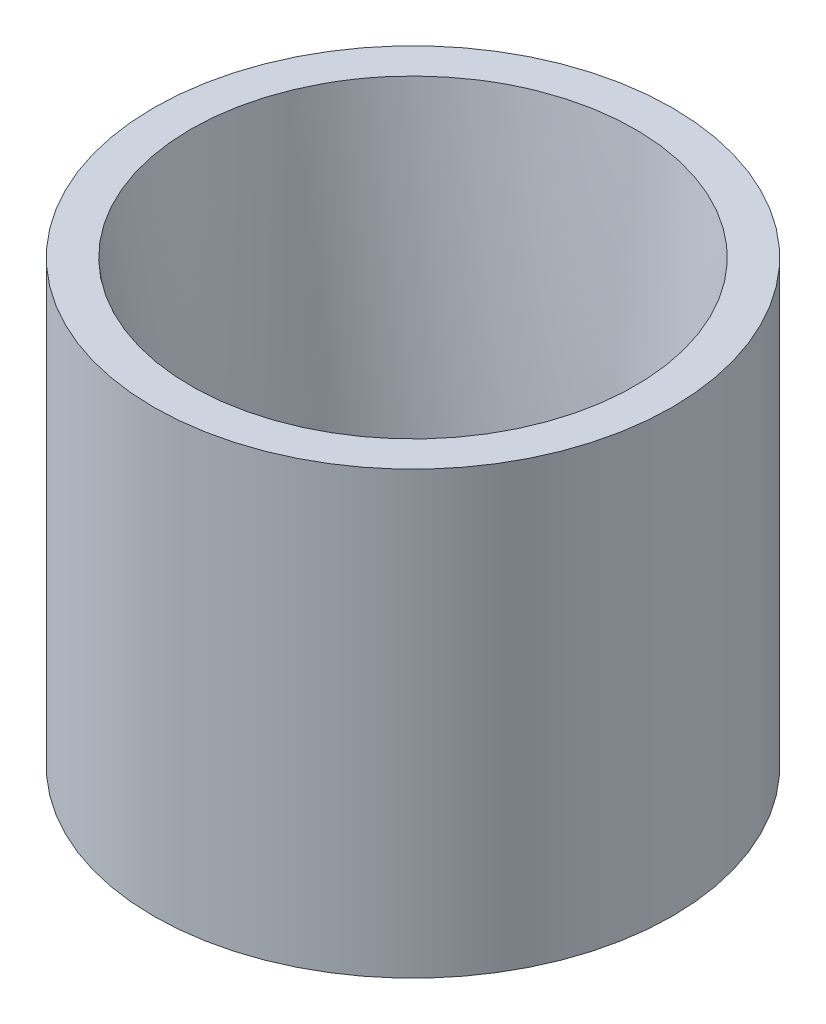
SolidWorks part; units mm, degrees
material "PVC 경질"
ref_plane "정면" through (0, 0, 0) normal (0, 0, 1) x (1, 0, 0)
ref_plane "윗면" through (0, 0, 0) normal (0, 1, 0) x (1, 0, 0)
ref_plane "우측면" through (0, 0, 0) normal (1, 0, 0) x (0, 0, -1)
other "질량 중심(COM)"
sketch "스케치1" plane through (0, 0, 0) normal (0, 1, 0) x (1, 0, 0)
  circle A0 centre (0, 0) radius 35
  dimension "D1" = 70
extrude "보스-돌출1" add sketch "스케치1" along normal blind 59.5
ref_plane "평면1" through (0, 5, 0) normal (0, 1, 0) x (1, 0, 0)
sketch "스케치2" plane through (0, 5, 0) normal (0, 1, 0) x (1, 0, 0)
  circle A0 centre (0, 0) radius 25.5
  dimension "D1" = 51
sketch "스케치3" plane through (0, 59.5, 0) normal (0, 1, 0) x (1, 0, 0)
  circle A0 centre (0, 0) radius 30
  dimension "D1" = 60
loft "컷-로프트1" cut profiles "스케치3", "스케치2" connector at (19.8958, 59.5, 22.4534) connector at (23.1274, 5, 10.7413)
